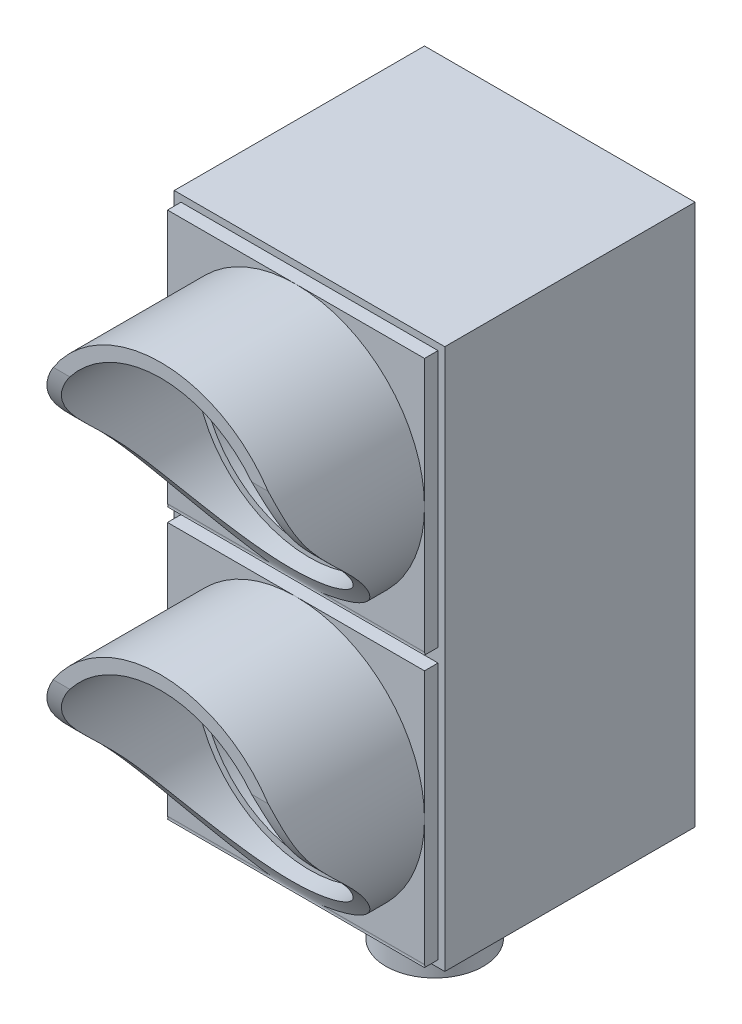
SolidWorks part; units mm, degrees
ref_plane "Front Plane" through (0, 0, 0) normal (0, 0, 1) x (1, 0, 0)
ref_plane "Top Plane" through (0, 0, 0) normal (0, 1, 0) x (1, 0, 0)
ref_plane "Right Plane" through (0, 0, 0) normal (1, 0, 0) x (0, 0, -1)
sketch "Sketch1" plane through (0, 0, 0) normal (0, 0, 1) x (1, 0, 0)
  line L1 (-77.3438, 208.5938) -> (-37.3437, 208.5938)
  line L2 (-77.3438, 208.5938) -> (-77.3438, 168.5938)
  line L3 (-77.3438, 168.5938) -> (-37.3437, 168.5938)
  line L4 (-37.3437, 208.5938) -> (-37.3437, 168.5938)
  dimension "D1" = 40
extrude "Boss-Extrude1" add sketch "Sketch1" along normal blind 15
sketch "Sketch4" plane through (0, 0, 15) normal (0, 0, 1) x (1, 0, 0)
  line L0 (-37.3437, 208.5938) -> (-77.3438, 208.5938) construction
  line L1 (-76.3438, 207.5938) -> (-38.3437, 207.5938)
  line L2 (-76.3438, 207.5938) -> (-76.3438, 169.5938)
  line L3 (-76.3438, 169.5938) -> (-38.3437, 169.5938)
  line L4 (-38.3437, 207.5938) -> (-38.3437, 169.5938)
  line L6 (-77.3438, 168.5938) -> (-37.3437, 168.5938) construction
  line L7 (-77.3438, 208.5938) -> (-77.3438, 168.5938) construction
  line L8 (-37.3437, 168.5938) -> (-37.3437, 208.5938) construction
  dimension "D1" = 1
  dimension "D2" = 1
  dimension "D3" = 1
  dimension "D4" = 1
extrude "Boss-Extrude2" add sketch "Sketch4" along normal blind 2
sketch "Sketch6" plane through (0, 0, 17) normal (0, 0, 1) x (1, 0, 0)
  line L0 (-38.3437, 207.5938) -> (-76.3438, 207.5938) construction
  line L2 (-76.3438, 207.5938) -> (-76.3438, 169.5938) construction
  circle A0 centre (-57.3438, 188.5938) radius 19
  circle A1 centre (-57.3438, 188.5938) radius 17
  point P3 (0, 0)
  point P4 (15.4957, 188.5938)
  point P6 (0, 0)
  point P9 (-76.3438, 188.5938)
  point P11 (-57.3438, 207.5938)
  dimension "D1" = 2
extrude "Boss-Extrude4" add sketch "Sketch6" along normal blind 20
sketch "Sketch8" plane through (-38.3437, 0, 0) normal (1, 0, 0) x (0, 0, -1)
  line L0 (-37, 207.5938) -> (-205.4996, 197.6233)
  line L1 (-205.4996, 197.6233) -> (-205.4996, 76.9339)
  line L2 (-205.4996, 76.9339) -> (-192.2498, 45.9268)
  line L3 (-192.2498, 45.9268) -> (-17, 68.8244)
  line L4 (-17, 68.8244) -> (-17, 169.5938)
  spline S0 degree 3 poles (-37, 207.5938) (-38.6023, 191.8521) (-28.7005, 190.0411) (-16.3844, 169.8832) (-17, 169.5938) knots 0 0 0 0 0.615781 1 1 1 1
  point P2 (0, 0)
  point P11 (-68, 207.5938)
  point P12 (-101.1595, 207.5938)
  point P14 (-89.6441, 189.0127)
  point P15 (-74.317, 179.0168)
  point P16 (-87.4495, 189.737)
  point P17 (-65.4318, 185.4586)
  point P18 (-41.8859, 177.2398)
  point P19 (-52.9924, 184.7922)
  point P20 (0, 0)
  point P21 (0, 0)
  point P22 (-55.0206, 188.1589)
  point P23 (-38.7631, 179.3951)
  point P24 (-52.2263, 187.7779)
  point P25 (-36.067, 187.2454)
  point P26 (-22.8159, 181.0544)
  point P27 (-31.5051, 188.766)
  point P28 (-24.771, 181.8147)
extrude "Enlèv. mat.-Extru.1" cut sketch "Sketch8" against normal through all
sketch "Esquisse3" plane through (0, 0, 17) normal (0, 0, 1) x (1, 0, 0)
  circle A0 centre (-57.3438, 188.5938) radius 17
  circle A1 centre (-57.3438, 188.5938) radius 17 construction
  circle A2 centre (-57.3438, 188.5938) radius 16
  dimension "D1" = 1
extrude "Enlèv. mat.-Extru.7" cut sketch "Esquisse3" against normal through all contours A2 region at (-57.3438, 188.5938, 17)
extrude "Enlèv. mat.-Extru.8" cut sketch "Esquisse3<4>" against normal blind 2
sketch "Esquisse3<4>" plane through (0, 0, 17) normal (0, 0, 1) x (1, 0, 0) same geometry as "Esquisse3"
extrude "Enlèv. mat.-Extru.9" cut sketch "Sketch4<2>" against normal through all from offset 2 offset against normal yes
sketch "Sketch4<2>" plane through (0, 0, 15) normal (0, 0, 1) x (1, 0, 0) same geometry as "Sketch4"
sketch "Esquisse7" plane through (0, 0, 0) normal (0, 0, -1) x (-1, 0, 0)
  line L1 (37.3437, 208.5938) -> (77.3438, 208.5938)
  line L2 (37.3437, 208.5938) -> (37.3437, 168.5938)
  line L3 (37.3437, 168.5938) -> (77.3438, 168.5938)
  line L4 (77.3438, 208.5938) -> (77.3438, 168.5938)
extrude "Boss.-Extru.1" add sketch "Esquisse7" along normal blind 2
sketch "Esquisse8" plane through (0, 0, -2) normal (0, 0, -1) x (-1, 0, 0)
  circle A0 centre (57.3438, 188.5938) radius 1.5
  circle A1 centre (57.3438, 188.5938) radius 16 construction
  dimension "D1" = 3
extrude "Enlèv. mat.-Extru.10" cut sketch "Esquisse8" against normal blind 2
pattern_linear "Répétition linéaire1" count 2 spacing 40 along (0, 1, 0) of bodies 122 120
sketch "Esquisse9" plane through (0, 0, -2) normal (0, 0, -1) x (-1, 0, 0)
  line L1 (37.3437, 248.5938) -> (77.3438, 248.5938)
  line L2 (37.3437, 248.5938) -> (37.3437, 168.5938)
  line L3 (37.3437, 168.5938) -> (77.3438, 168.5938)
  line L4 (77.3438, 248.5938) -> (77.3438, 168.5938)
  line L5 (39.3438, 246.5938) -> (75.3437, 246.5938)
  line L6 (39.3438, 246.5938) -> (39.3438, 170.5938)
  line L7 (39.3438, 170.5938) -> (75.3437, 170.5938)
  line L8 (75.3437, 246.5938) -> (75.3437, 170.5938)
  point P10 (57.3438, 246.5938)
  point P11 (57.3438, 248.5938)
  point P12 (39.3438, 208.5938)
  dimension "D1" = 36
  dimension "D2" = 76
extrude "Boss.-Extru.2" add sketch "Esquisse9" along normal blind 20
sketch "Esquisse10" plane through (0, 0, -2) normal (0, 0, -1) x (-1, 0, 0)
  line L0 (75.3437, 246.5938) -> (39.3438, 246.5938) construction
  line L1 (39.3438, 246.5938) -> (39.3438, 170.5938) construction
  line L2 (70.3438, 175.5938) -> (75.3437, 175.5938)
  line L3 (39.3438, 246.5938) -> (44.3438, 246.5938)
  line L4 (39.3438, 246.5938) -> (39.3438, 241.5938)
  line L5 (39.3438, 241.5938) -> (44.3438, 241.5938)
  line L6 (44.3438, 246.5938) -> (44.3438, 241.5938)
  line L7 (70.3438, 175.5938) -> (70.3438, 170.5938)
  line L8 (70.3438, 170.5938) -> (75.3437, 170.5938)
  line L9 (75.3437, 175.5938) -> (75.3437, 170.5938)
  line L10 (75.3437, 170.5938) -> (75.3437, 246.5938) construction
  line L11 (39.3438, 170.5938) -> (75.3437, 170.5938) construction
  circle A0 centre (41.8438, 244.0938) radius 2.5
  circle A1 centre (41.8438, 244.0938) radius 1.5
  circle A2 centre (72.8437, 173.0938) radius 2.5
  circle A3 centre (72.8437, 173.0938) radius 1.5
  line M3 (75.3437, 246.5938) -> (39.3438, 246.5938)
  line M4 (39.3438, 246.5938) -> (39.3438, 170.5938)
  line M5 (39.3438, 170.5938) -> (75.3437, 170.5938)
  line M6 (75.3437, 170.5938) -> (75.3437, 246.5938)
  dimension "D1" = 5
  dimension "D2" = 3
extrude "Boss.-Extru.8" add sketch "Esquisse10" along direction (0, 0, 1) on the side of the normal blind 12 contours A0 L4 L5 | A0 L5 L6 | A0 L6 M3 | A0 L3 M4 | A0 A1 | A2 L7 M5 | A2 L2 L7 | A2 A3 | A2 L9 L2 | A2 L8 M6 region at (-70.9022, 175.0353, -2) region at (-74.7853, 175.0353, -2) region at (-74.5615, 174.8115, -2) region at (-70.9022, 171.1522, -2) region at (-74.7853, 171.1522, -2) region at (-43.7853, 246.0353, -2) region at (-39.9022, 242.1522, -2) region at (-39.9022, 246.0353, -2) region at (-43.5615, 245.8115, -2) region at (-43.7853, 242.1522, -2)
extrude "Boss.-Extru.9" add sketch "Esquisse10<4>" along normal blind 7 contours A1 | A3 region at (-41.8438, 244.0938, -2) region at (-72.8437, 173.0938, -2)
sketch "Esquisse10<4>" plane through (0, 0, -2) normal (0, 0, -1) x (-1, 0, 0) same geometry as "Esquisse10"
sketch "Esquisse11" plane through (0, 168.5938, 0) normal (0, -1, 0) x (1, 0, 0)
  line L0 (-37.3437, -22) -> (-37.3437, 15) construction
  line L1 (-37.3437, -22) -> (-77.3438, -22) construction
  circle A0 centre (-57.3438, -3.5) radius 5.2
  circle A1 centre (-57.3438, -3.5) radius 7.2
  point P4 (-37.3437, -3.5)
  point P7 (-57.3438, -22)
  dimension "D1" = 10.4
  dimension "D2" = 14.4
extrude "Boss.-Extru.10" add sketch "Esquisse11" along normal blind 15
extrude "Enlèv. mat.-Extru.12" cut sketch "Esquisse11<2>" against normal up to surface (2 mm away) contours A0 region at (-57.3438, 168.5938, -3.5) up to face at (-61.6771, 170.5938, -12.6667)
sketch "Esquisse11<2>" plane through (0, 168.5938, 0) normal (0, -1, 0) x (1, 0, 0) same geometry as "Esquisse11"
sketch "Esquisse13" plane through (-77.3438, 0, 0) normal (-1, 0, 0) x (0, 0, 1)
  line L0 (-22, 168.5938) -> (-22, 248.5938) construction
  line L1 (-17, 187.5938) -> (-8, 187.5938)
  line L2 (-17, 187.5938) -> (-17, 183.5938)
  line L3 (-17, 183.5938) -> (-8, 183.5938)
  line L4 (-8, 187.5938) -> (-8, 183.5938)
  line L5 (-22, 168.5938) -> (15, 168.5938) construction
  dimension "D1" = 9
  dimension "D2" = 4
  dimension "D3" = 5
  dimension "D4" = 15
extrude "Enlèv. mat.-Extru.13" cut sketch "Esquisse13" against normal blind 2
equation "\"D1@Esquisse9\"=36"
